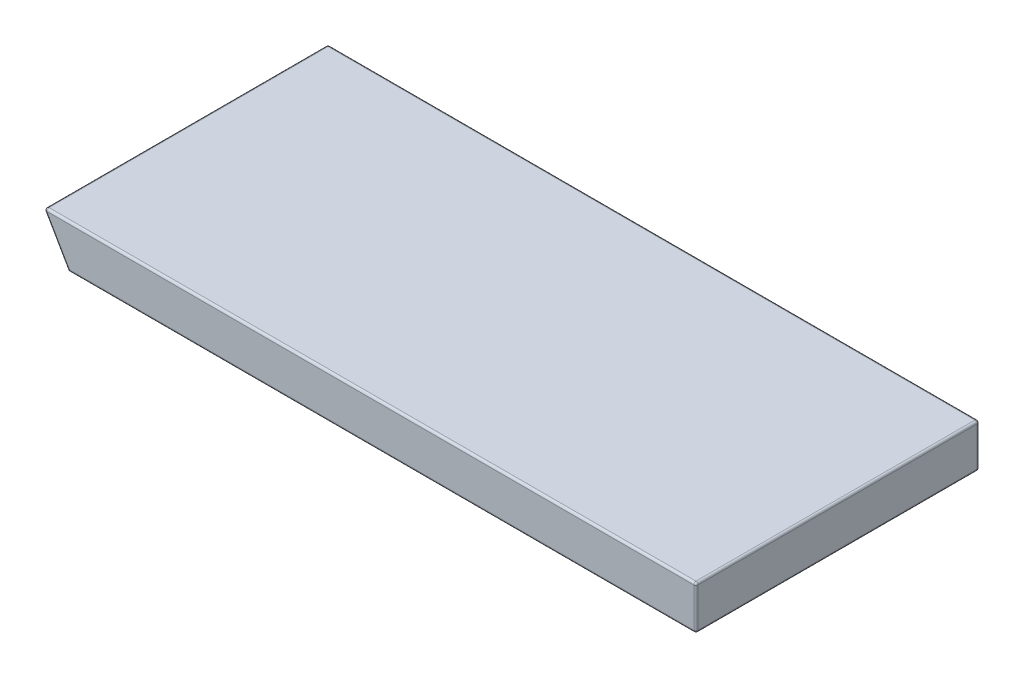
SolidWorks part; units mm, degrees
ref_plane "Front Plane" through (0, 0, 0) normal (0, 0, 1) x (1, 0, 0)
ref_plane "Top Plane" through (0, 0, 0) normal (0, 1, 0) x (1, 0, 0)
ref_plane "Right Plane" through (0, 0, 0) normal (1, 0, 0) x (0, 0, -1)
sketch "Sketch1" plane through (0, 0, 0) normal (0, 1, 0) x (1, 0, 0)
  line L1 (77, 32.5) -> (-77, 32.5)
  line L2 (77, 32.5) -> (77, -32.5)
  line L3 (77, -32.5) -> (-77, -32.5)
  line L4 (-77, 32.5) -> (-77, -32.5)
  line L5 (77, 32.5) -> (-77, -32.5) construction
  line L6 (77, -32.5) -> (-77, 32.5) construction
  point P0 (0, 0)
  dimension "D1" = 154
  dimension "D2" = 65
extrude "base" add sketch "Sketch1" along normal blind 10 contours L1 L4 L3 L2
sketch "Sketch2" plane through (0, 0, 0) normal (0, -1, 0) x (1, 0, 0)
  circle A0 centre (0, 0) radius 3
  dimension "D1" = 6
extrude "load cell button cut" [suppressed] cut sketch "Sketch2" against normal blind 2
sketch "Sketch4" plane through (0, 0, 0) normal (1, 0, 0) x (0, 0, -1)
  line L0 (3, 0) -> (3, 2)
  line L1 (3, 2) -> (0, 3.7321)
  line L2 (0, 3.7321) -> (0, 0) construction
  line L3 (0, 0) -> (3, 0)
  line L4 (0, 3.7321) -> (0, 0)
  dimension "D1" = 3
  dimension "D2" = 2
  dimension "D3" = 60
revolve "Cut-Revolve1" [suppressed] cut sketch "Sketch4" angle 360 about L2
sketch "Sketch5" plane through (0, 0, 32.5) normal (0, 0, 1) x (1, 0, 0)
  line L0 (-72.7735, 10) -> (-67, 0)
  line L1 (77, 0) -> (-77, 0) construction
  line L2 (-67, 0) -> (-67, 10) construction
  line L3 (77, 10) -> (-77, 10) construction
  line L5 (-77, 0) -> (-67, 0)
  point P9 (0, 0)
  point P11 (-73.9344, 10)
  dimension "D1" = 30
  dimension "D2" = 10
extrude "Cut-Extrude1" cut sketch "Sketch5" against normal through all
fillet "Fillet1" radius 0.5 12 edges at (77, 5, -32.5) (77, 5, 32.5) (2.1132, 10, -32.5) (2.1132, 10, 32.5) (77, 10, 0) (5, 0, -32.5) (5, 0, 32.5) (77, 0, 0) (-67, 0, 0) (-69.8868, 5, -32.5) (-72.7735, 10, 0) (-69.8868, 5, 32.5)
equation "\"D2@Sketch1\"=65"
equation "\"D1@Sketch1\"=144+10"
